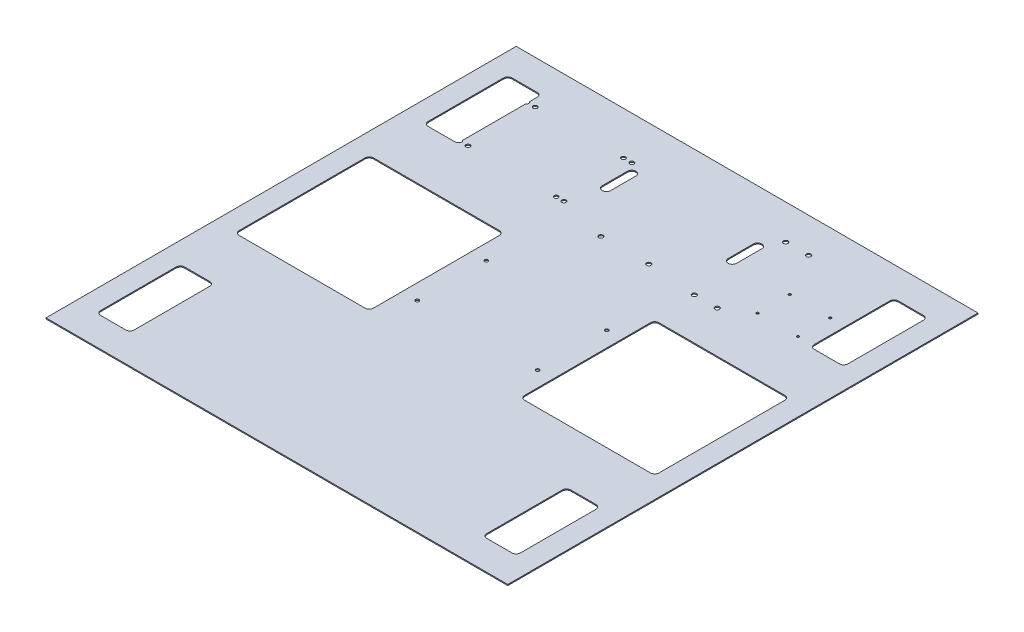
SolidWorks part; units mm, degrees
ref_plane "Front Plane" through (0, 0, 0) normal (0, 0, 1) x (1, 0, 0)
ref_plane "Top Plane" through (0, 0, 0) normal (0, 1, 0) x (1, 0, 0)
ref_plane "Right Plane" through (0, 0, 0) normal (1, 0, 0) x (0, 0, -1)
sketch "Sketch1" plane through (0, 0, 0) normal (0, 1, 0) x (1, 0, 0)
  line L6 (0, 0) -> (698.5, 0)
  line L11 (0, 0) -> (0, -711.2)
  line L12 (0, -711.2) -> (698.5, -711.2)
  line L17 (698.5, 0) -> (698.5, -711.2)
  line L18 (349.25, -711.2) -> (349.25, 0) construction
  line L22 (0, -355.6) -> (698.5, -355.6) construction
  line L24 (31.75, -254) -> (234.95, -254)
  line L25 (31.75, -254) -> (31.75, -457.2)
  line L26 (31.75, -457.2) -> (234.95, -457.2)
  line L27 (234.95, -254) -> (234.95, -457.2)
  line L28 (133.35, -457.2) -> (133.35, -254) construction
  line L29 (31.75, -355.6) -> (234.95, -355.6) construction
  line L30 (463.55, -254) -> (666.75, -254)
  line L31 (463.55, -254) -> (463.55, -457.2)
  line L32 (463.55, -457.2) -> (666.75, -457.2)
  line L33 (666.75, -254) -> (666.75, -457.2)
  line L34 (565.15, -457.2) -> (565.15, -254) construction
  line L35 (474.012, -355.6) -> (666.75, -355.6) construction
  point P60 (133.35, -355.6)
  point P77 (565.15, -355.6)
  point P133 (349.25, -355.6)
  dimension "D1" = 203.2
  dimension "D2" = 203.2
  dimension "D3" = 698.5
  dimension "D4" = 711.2
  dimension "D5" = 31.75
  dimension "D6" = 31.75
  dimension "D7" = 254
extrude "Boss-Extrude1" add sketch "Sketch1" along normal blind 1.5875
fillet "Fillet1" radius 6.35 8 edges at (666.75, 0.7937, 457.2) (666.75, 0.7937, 254) (463.55, 0.7937, 254) (463.55, 0.7937, 457.2) (234.95, 0.7937, 457.2) (31.75, 0.7937, 457.2) (234.95, 0.7937, 254) (31.75, 0.7937, 254)
sketch "Sketch2" plane through (0, 1.5875, 0) normal (0, 1, 0) x (1, 0, 0)
  circle A0 centre (440.3852, -407.797) radius 2.667
  circle A1 centre (258.1148, -407.797) radius 2.667
  circle A2 centre (258.1148, -303.403) radius 2.667
  circle A3 centre (440.3852, -303.403) radius 2.667
  circle A8 centre (460.248, -190.7255) radius 3.429
  circle A9 centre (494.792, -190.7255) radius 3.429
  circle A10 centre (460.2785, -52.578) radius 3.429
  circle A11 centre (494.8225, -52.578) radius 3.429
  circle A16 centre (227.3074, -65.1097) radius 3.175
  circle A17 centre (227.3074, -166.7097) radius 3.175
  circle A18 centre (93.8645, -166.7097) radius 3.175
  circle A19 centre (93.8645, -65.1097) radius 3.175
  circle A20 centre (81.1645, -65.1097) radius 3.175
  circle A21 centre (81.1645, -166.7097) radius 3.175
  circle A22 centre (238.8995, -166.7097) radius 3.175
  circle A23 centre (240.0074, -65.1097) radius 3.175
  circle A24 centre (385.445, -184.8962) radius 3.3782
  circle A25 centre (313.055, -184.8962) radius 3.3782
  circle A30 centre (593.1251, -166.9626) radius 1.8382
  circle A31 centre (532.0981, -166.9626) radius 1.8387
  circle A32 centre (532.0833, -118.1258) radius 1.8387
  circle A33 centre (593.1102, -118.1258) radius 1.8382
  dimension "D1" = 6.35
  dimension "D2" = 12.7
  dimension "D3" = 12.7
  dimension "D4" = 12.7
  dimension "D5" = 101.6
extrude "Cut-Extrude1" cut sketch "Sketch2" against normal through all
sketch "Sketch3" plane through (0, 1.5875, 0) normal (0, 1, 0) x (1, 0, 0)
  line L0 (0, 0) -> (0, -711.2) construction
  line L1 (666.75, -171.45) -> (615.95, -171.45)
  line L2 (666.75, -171.45) -> (666.75, -44.45)
  line L3 (666.75, -44.45) -> (615.95, -44.45)
  line L4 (615.95, -171.45) -> (615.95, -44.45)
  line L5 (31.75, -171.45) -> (82.55, -171.45)
  line L6 (31.75, -171.45) -> (31.75, -44.45)
  line L7 (31.75, -44.45) -> (82.55, -44.45)
  line L8 (82.55, -171.45) -> (82.55, -44.45)
  line L9 (31.75, -666.75) -> (82.55, -666.75)
  line L10 (31.75, -666.75) -> (31.75, -539.75)
  line L11 (31.75, -539.75) -> (82.55, -539.75)
  line L12 (82.55, -666.75) -> (82.55, -539.75)
  line L13 (666.75, -666.75) -> (615.95, -666.75)
  line L14 (666.75, -666.75) -> (666.75, -539.75)
  line L15 (666.75, -539.75) -> (615.95, -539.75)
  line L16 (615.95, -666.75) -> (615.95, -539.75)
  line L17 (698.5, 0) -> (0, 0) construction
  line L18 (0, -711.2) -> (698.5, -711.2) construction
  line L19 (698.5, -711.2) -> (698.5, 0) construction
  point P16 (623.5758, -564.3158)
  point P17 (628.3301, -501.5584)
  point P18 (99.6468, -504.411)
  point P19 (84.4329, -493.0006)
  point P20 (622.6249, -523.4284)
  point P25 (615.95, -552.45)
  point P26 (0, 0)
  point P27 (0, 0)
  point P28 (0, 0)
  point P29 (0, 0)
  point P30 (204.7813, -552.45)
  dimension "D1" = 44.45
  dimension "D2" = 31.75
  dimension "D3" = 127
  dimension "D4" = 50.8
  dimension "D5" = 31.75
  dimension "D6" = 44.45
extrude "Cut-Extrude2" cut sketch "Sketch3" against normal through all
sketch "Sketch4" plane through (0, 1.5875, 0) normal (0, 1, 0) x (1, 0, 0)
  line L0 (698.5, 0) -> (0, 0) construction
  line L1 (450.85, -123.825) -> (438.15, -123.825)
  line L2 (450.85, -123.825) -> (450.85, -73.025)
  line L3 (450.85, -73.025) -> (438.15, -73.025)
  line L4 (438.15, -123.825) -> (438.15, -73.025)
  line L5 (260.35, -123.825) -> (247.65, -123.825)
  line L6 (260.35, -123.825) -> (260.35, -73.025)
  line L7 (260.35, -73.025) -> (247.65, -73.025)
  line L8 (247.65, -123.825) -> (247.65, -73.025)
  line L9 (698.5, -711.2) -> (698.5, 0) construction
  line L10 (0, 0) -> (0, -711.2) construction
  dimension "D1" = 50.8
  dimension "D2" = 73.025
  dimension "D3" = 12.7
  dimension "D4" = 247.65
  dimension "D5" = 247.65
extrude "Cut-Extrude3" cut sketch "Sketch4" against normal through all
fillet "Fillet2" radius 6.35 24 edges at (438.15, 0.7937, 73.025) (450.85, 0.7937, 73.025) (260.35, 0.7937, 73.025) (247.65, 0.7937, 73.025) (247.65, 0.7937, 123.825) (260.35, 0.7937, 123.825) (438.15, 0.7937, 123.825) (450.85, 0.7937, 123.825) (82.55, 0.7937, 44.45) (31.75, 0.7937, 44.45) (31.75, 0.7937, 171.45) (82.55, 0.7937, 171.45) (615.95, 0.7937, 44.45) (666.75, 0.7937, 44.45) (615.95, 0.7937, 171.45) (666.75, 0.7937, 171.45) (82.55, 0.7937, 539.75) (31.75, 0.7937, 539.75) (82.55, 0.7937, 666.75) (31.75, 0.7937, 666.75) (615.95, 0.7937, 539.75) (615.95, 0.7937, 666.75) (666.75, 0.7937, 666.75) (666.75, 0.7937, 539.75)
equation "\"D6@Sketch3\"=\"D1@Sketch3\""
equation "\"D5@Sketch3\"=\"D2@Sketch3\""
equation "\"D5@Sketch4\"=\"D4@Sketch4\""
